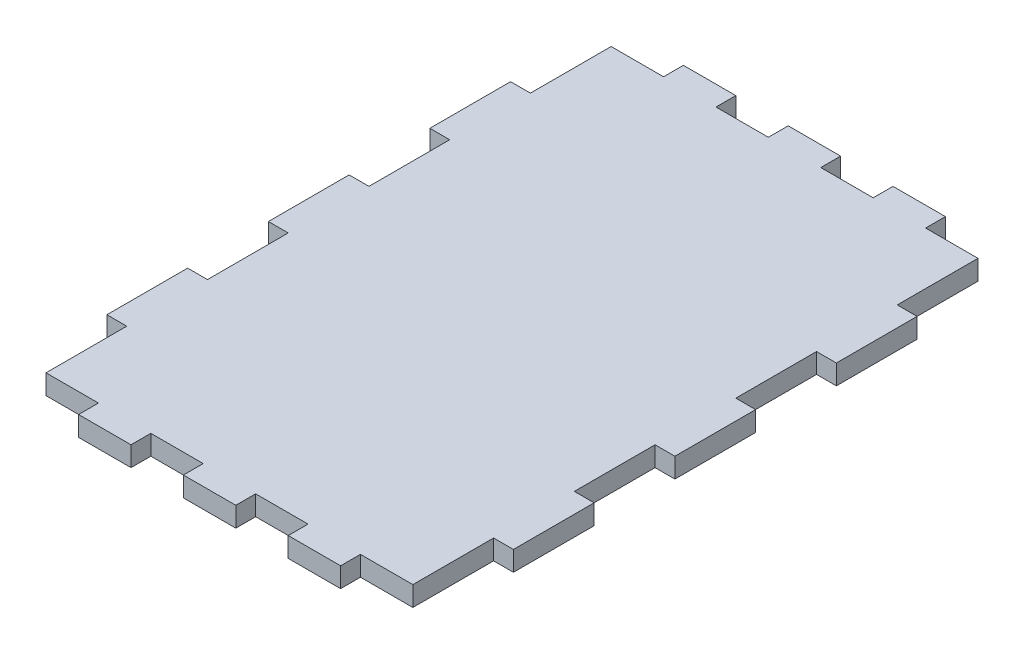
SolidWorks part; units mm, degrees
ref_plane "前视基准面" through (0, 0, 0) normal (0, 0, 1) x (1, 0, 0)
ref_plane "上视基准面" through (0, 0, 0) normal (0, 1, 0) x (1, 0, 0)
ref_plane "右视基准面" through (0, 0, 0) normal (1, 0, 0) x (0, 0, -1)
other "Configuration Table"
sketch "草图4" plane through (0, 0, 0) normal (0, 1, 0) x (1, 0, 0)
  line L6 (-18.5, -28.5) -> (18.5, -28.5)
  line L11 (-18.5, -28.5) -> (-18.5, 28.5)
  line L12 (-18.5, 28.5) -> (18.5, 28.5)
  line L13 (18.5, -28.5) -> (18.5, 28.5)
  line L14 (-18.5, -28.5) -> (18.5, 28.5) construction
  line L15 (-18.5, 28.5) -> (18.5, -28.5) construction
  point P0 (0, 0)
  dimension "D1" = 37
  dimension "D2" = 57
extrude "凸台-拉伸1" add sketch "草图4" along normal blind 2
sketch "草图5" plane through (0, 0, 28.5) normal (0, 0, 1) x (1, 0, 0)
  line L0 (-18.5, 2) -> (18.5, 2) construction
  line L1 (13.2143, 2) -> (7.9286, 2)
  line L2 (13.2143, 2) -> (13.2143, 0)
  line L3 (13.2143, 0) -> (7.9286, 0)
  line L4 (7.9286, 2) -> (7.9286, 0)
  line L5 (-18.5, 0) -> (18.5, 0) construction
  line L6 (-13.2143, 1) -> (-18.5, 1)
  line L7 (2.6429, 2) -> (-2.6429, 2)
  line L8 (2.6429, 2) -> (2.6429, 0)
  line L9 (2.6429, 0) -> (-2.6429, 0)
  line L10 (-2.6429, 2) -> (-2.6429, 0)
  line L11 (-7.9286, 2) -> (-13.2143, 2)
  line L12 (-7.9286, 2) -> (-7.9286, 0)
  line L13 (-7.9286, 0) -> (-13.2143, 0)
  line L14 (-13.2143, 2) -> (-13.2143, 0)
  line L15 (-18.5, 2) -> (-18.5, 0) construction
  line L16 (-7.9286, 1) -> (-2.6429, 1)
  line L17 (2.6429, 1) -> (7.9286, 1)
  line L18 (13.2143, 1) -> (18.5, 1)
  line L19 (18.5, 2) -> (18.5, 0) construction
extrude "凸台-拉伸2" add sketch "草图5" along normal blind 2 contours L1 L4 L3 L2 | L7 L10 L9 L8 | L11 L14 L13 L12
extrude "凸台-拉伸3" add sketch "草图5<3>" against normal blind 2 from surface contours L1 L4 L3 L2 | L7 L10 L9 L8 | L11 L14 L13 L12 starting at face at (0, 1, -28.5)
sketch "草图5<3>" plane through (0, 0, 28.5) normal (0, 0, 1) x (1, 0, 0) same geometry as "草图5"
sketch "草图6" plane through (18.5, 0, 0) normal (1, 0, 0) x (0, 0, -1)
  line L10 (-28.5, 0) -> (-28.5, 2) construction
  line L19 (28.5, 0) -> (28.5, 2) construction
  line L20 (-28.5, 2) -> (28.5, 2) construction
  line L21 (-20.3571, 2) -> (-12.2143, 2)
  line L22 (-20.3571, 2) -> (-20.3571, 0)
  line L23 (-20.3571, 0) -> (-12.2143, 0)
  line L24 (-12.2143, 2) -> (-12.2143, 0)
  line L25 (-28.5, 0) -> (28.5, 0) construction
  line L26 (-28.5, 1) -> (-20.3571, 1) construction
  line L27 (-4.0714, 2) -> (4.0714, 2)
  line L28 (-4.0714, 2) -> (-4.0714, 0)
  line L29 (-4.0714, 0) -> (4.0714, 0)
  line L30 (4.0714, 2) -> (4.0714, 0)
  line L31 (12.2143, 2) -> (20.3571, 2)
  line L32 (12.2143, 2) -> (12.2143, 0)
  line L33 (12.2143, 0) -> (20.3571, 0)
  line L34 (20.3571, 2) -> (20.3571, 0)
  line L35 (-20.3571, 1) -> (-12.2143, 1) construction
  line L36 (-12.2143, 1) -> (-4.0714, 1) construction
  line L37 (-4.0714, 1) -> (4.0714, 1) construction
  line L38 (4.0714, 1) -> (12.2143, 1) construction
  line L39 (12.2143, 1) -> (20.3571, 1) construction
  line L40 (20.3571, 1) -> (28.5, 1) construction
extrude "凸台-拉伸4" add sketch "草图6" along normal blind 2
extrude "凸台-拉伸5" add sketch "草图6<2>" against normal blind 2 from surface starting at face at (-18.5, 1, 0)
sketch "草图6<2>" plane through (18.5, 0, 0) normal (1, 0, 0) x (0, 0, -1) same geometry as "草图6"
